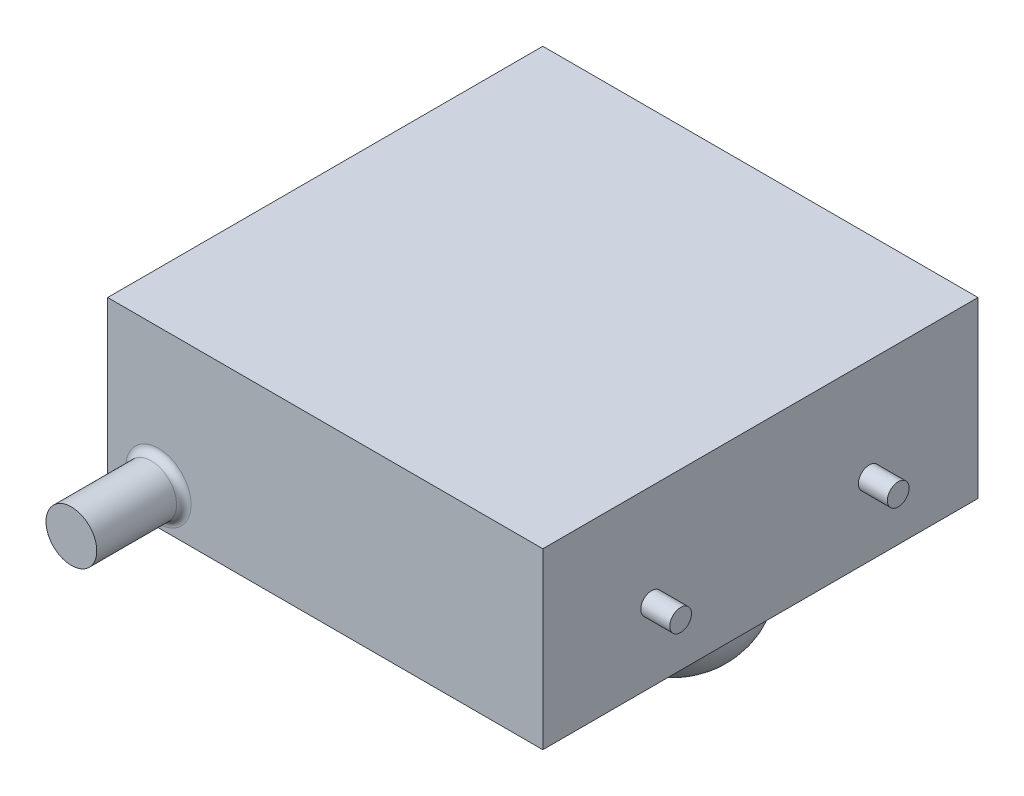
SolidWorks part; units mm, degrees
ref_plane "Front Plane" through (0, 0, 0) normal (0, 0, 1) x (1, 0, 0)
ref_plane "Top Plane" through (0, 0, 0) normal (0, 1, 0) x (1, 0, 0)
ref_plane "Right Plane" through (0, 0, 0) normal (1, 0, 0) x (0, 0, -1)
sketch "Sketch1" plane through (0, 0, 0) normal (0, 1, 0) x (1, 0, 0)
  line L1 (-150, 150) -> (150, 150)
  line L2 (-150, 150) -> (-150, -150)
  line L3 (-150, -150) -> (150, -150)
  line L4 (150, 150) -> (150, -150)
  line L5 (-150, 150) -> (150, -150) construction
  line L6 (-150, -150) -> (150, 150) construction
  point P0 (0, 0)
  dimension "D1" = 300
  dimension "D2" = 300
extrude "Boss-Extrude1" add sketch "Sketch1" along normal blind 120
sketch "Sketch3" plane through (0, 0, 150) normal (0, 0, 1) x (1, 0, 0)
  line L0 (-150, 0) -> (150, 0) construction
  line L1 (-150, 120) -> (-150, 0) construction
  circle A0 centre (-115, 25) radius 17.5
  dimension "D1" = 35
  dimension "D2" = 25
  dimension "D3" = 35
extrude "Boss-Extrude3" add sketch "Sketch3" along normal blind 60
mirror "Mirror1" about plane through (0, 0, 0) normal (0, 0, 1) of "Boss-Extrude3"
fillet "Fillet1" radius 5 2 edges at (-132.5, 25, 150) (-97.5, 25, -150)
sketch "Sketch4" plane through (0, 0, 0) normal (0, -1, 0) x (1, 0, 0)
  circle A0 centre (90, 0) radius 51
  dimension "D1" = 102
  dimension "D2" = 90
extrude "Boss-Extrude4" add sketch "Sketch4" along normal blind 50
fillet "Fillet2" radius 50 1 edges at (90, -50, -51)
sketch "Sketch6" plane through (150, 0, 0) normal (1, 0, 0) x (0, 0, -1)
  line L0 (-150, 120) -> (150, 120) construction
  circle A0 centre (-75, 50) radius 7.5
  circle A1 centre (75, 50) radius 7.5
  dimension "D1" = 15
  dimension "D2" = 15
  dimension "D3" = 70
extrude "Boss-Extrude5" add sketch "Sketch6" along normal blind 20
